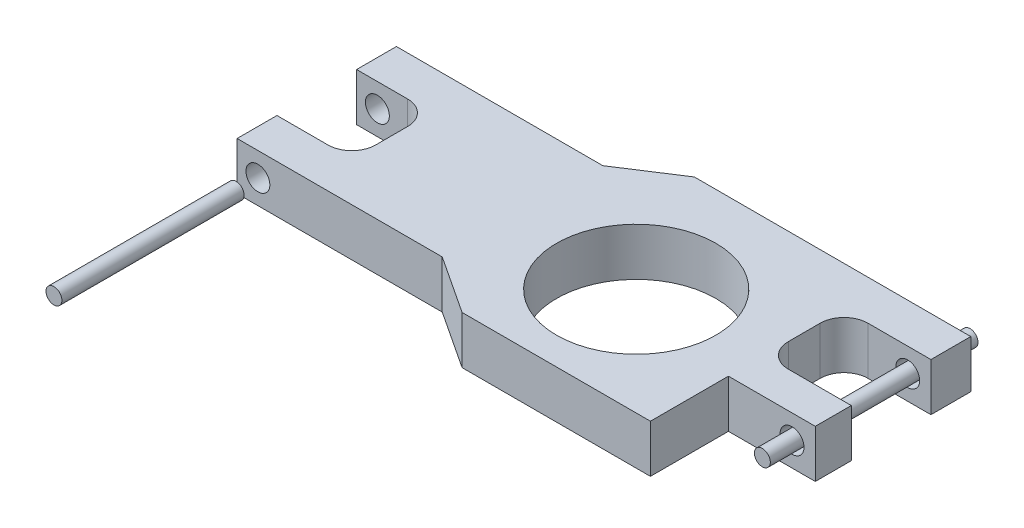
SolidWorks part; units mm, degrees
ref_plane "Front Plane" through (0, 0, 0) normal (0, 0, 1) x (1, 0, 0)
ref_plane "Top Plane" through (0, 0, 0) normal (0, 1, 0) x (1, 0, 0)
ref_plane "Right Plane" through (0, 0, 0) normal (1, 0, 0) x (0, 0, -1)
sketch "Sketch21" plane through (0, 0, 0) normal (0, 1, 0) x (1, 0, 0)
  line L0 (-35.2989, 23.7883) -> (-68.2028, 23.7883)
  line L1 (-68.2028, 23.7883) -> (-68.2028, 17.4383)
  line L2 (-35.4979, -1.6117) -> (-68.2028, -1.6117)
  line L3 (-68.2028, 17.4383) -> (-60.0738, 17.4383)
  line L4 (-56.2638, 13.6283) -> (-56.2638, 8.5483)
  line L5 (-60.0738, 4.7383) -> (-68.2028, 4.7383)
  line L6 (-68.2028, 4.7383) -> (-68.2028, -1.6117)
  line L7 (-63.1228, 93.9808) -> (21.5481, 93.9808) construction
  line L8 (52.8639, 77.8829) -> (52.8639, -77.8829) construction
  line L9 (-26.2419, -7.6986) -> (3.7825, -7.6986)
  line L10 (17.631, 4.7383) -> (17.631, 10.4782)
  line L11 (17.631, 23.1782) -> (7.5925, 23.1782)
  line L12 (3.7825, 19.3682) -> (3.7825, 14.2882)
  line L13 (7.5925, 10.4782) -> (17.631, 10.4782)
  line L14 (17.631, 29.5282) -> (-26.4371, 29.5282)
  line L15 (17.631, 23.1782) -> (17.631, 29.5282)
  line L16 (-35.2989, 23.7883) -> (-26.4371, 29.5282)
  line L17 (-101.5364, -32.0917) -> (-101.5364, 0) construction
  line L18 (3.7825, -7.6986) -> (3.7825, 4.7383)
  line L20 (0, 0) -> (-110.6978, 0) construction
  line L21 (3.7825, 4.7383) -> (17.631, 4.7383)
  line L22 (-35.4979, -1.6117) -> (-26.2419, -7.6986)
  circle A0 centre (-15.5704, 9.3886) radius 12.7
  arc A1 (7.5925, 23.1782) -> (3.7825, 19.3682) centre (7.5925, 19.3682) ccw
  arc A2 (3.7825, 14.2882) -> (7.5925, 10.4782) centre (7.5925, 14.2882) ccw
  arc A3 (-60.0738, 17.4383) -> (-56.2638, 13.6283) centre (-60.0738, 13.6283) cw
  arc A4 (-56.2638, 8.5483) -> (-60.0738, 4.7383) centre (-60.0738, 8.5483) cw
  dimension "D9" = 25.4
  dimension "D7" = 3.81
  dimension "D8" = 1.6117
  dimension "D1" = 84.6709
  dimension "D3" = 5.08
  dimension "D4" = 25.4
  dimension "D5" = 6.35
extrude "Extrude1" add sketch "Sketch21" along normal mid plane 7.62 contours L2 L6 L5 A4 L4 A3 L3 L1 L0 L16 L14 L15 L11 A1 L12 A2 L13 L10 L21 L18 L9 L22 | A0
sketch "Sketch22" plane through (0, 0, -29.5282) normal (0, 0, -1) x (-1, 0, 0)
  line L0 (-17.631, 0) -> (77.4589, 0) construction
  circle A0 centre (-13.9288, 0) radius 1.905
  circle A1 centre (64.8874, 0.0093) radius 1.905
  dimension "D1" = 78.8162
  dimension "D3" = 3.81
extrude "Cut-Extrude1" cut sketch "Sketch22" against normal mid plane 183.515
sketch "Sketch23" plane through (0, 0, 0) normal (0, 0, 1) x (1, 0, 0)
  circle A0 centre (-64.8874, 0.0093) radius 1.27
  circle A1 centre (13.9288, 0) radius 1.27
  dimension "D1" = 2.54
extrude "Extrude2" add sketch "Sketch23" against normal blind 33.114 separate body contours A1
extrude "Extrude3" add sketch "Sketch23<3>" along normal blind 29.05 from offset 5.08 separate body contours A0
sketch "Sketch23<3>" plane through (0, 0, 0) normal (0, 0, 1) x (1, 0, 0) same geometry as "Sketch23"
